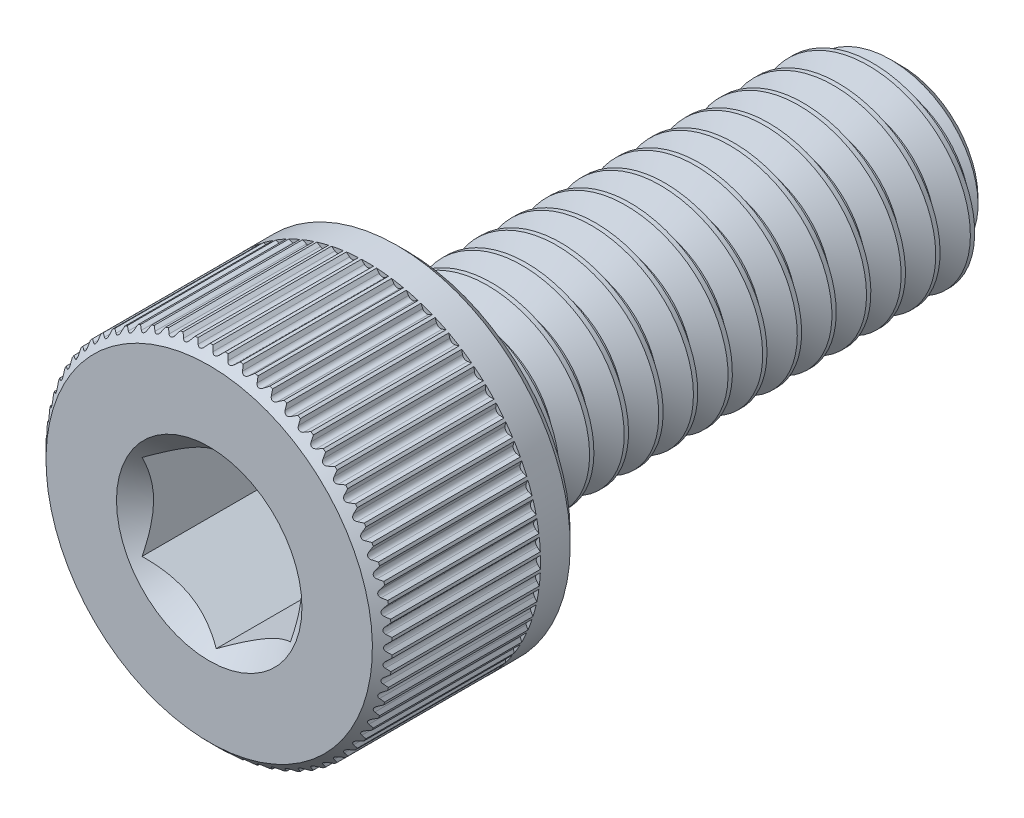
SolidWorks part; units mm, degrees
ref_plane "Front Plane" through (0, 0, 0) normal (0, 0, 1) x (1, 0, 0)
ref_plane "Top Plane" through (0, 0, 0) normal (0, 1, 0) x (1, 0, 0)
ref_plane "Right Plane" through (0, 0, 0) normal (1, 0, 0) x (0, 0, -1)
sketch "Sketch1" plane through (0, 0, 0) normal (1, 0, 0) x (0, 0, -1)
  line L0 (-7, 0) -> (7, 0) construction
  line L1 (7, 0) -> (7, 1.5453) construction
  line L2 (7, 1.5453) -> (6.5453, 2) construction
  line L3 (6.5453, 2) -> (6.475, 2) construction
  line L4 (6.475, 2) -> (-3, 2) construction
  line L5 (-3, 2) -> (-3, 3.5) construction
  line L6 (-3, 3.5) -> (-7, 3.5) construction
  line L7 (-7, 3.5) -> (-7, 0) construction
  line L8 (7, 1.5453) -> (7, 2) construction
  line L9 (6.9562, 2.0758) -> (7.3062, 1.4696) construction
  line L10 (7.3062, 1.4696) -> (7.6562, 2.0758) construction
  line L11 (7.6562, 2.0758) -> (6.9562, 2.0758) construction
  line L12 (7.3062, 2.0758) -> (7.3062, 2) construction
  line L13 (7.3062, 1.4696) -> (7.3062, 1.5453) construction
  line L14 (7.2625, 1.5453) -> (7.35, 1.5453) construction
  line L15 (7, 2) -> (7.6125, 2) construction
  line L16 (6.9781, 2.0379) -> (7.6344, 2.0379) construction
  line L17 (7, 0) -> (7, -2) construction
  line L18 (-3.2, 3.5) -> (-3, 3.3) construction
  line L19 (-6.8, 3.5) -> (-7, 3.3) construction
  line L20 (-3, 2) -> (-3, 0) construction
  line L21 (-3, 1) -> (0.3333, 1) construction
  line L22 (0.3333, 1) -> (3.6667, 1) construction
  line L23 (3.6667, 1) -> (7, 1) construction
  line L24 (0.3333, 1) -> (0.3333, 2) construction
  line L25 (0.3333, 2) -> (0.3333, 3.5) construction
  line L26 (3.6667, 1) -> (3.6667, 3.5) construction
  point P0 (-7, 1.5)
  point P3 (5.25, 2)
  point P4 (0, 0)
  point P18 (3.6667, 2)
  point P22 (7.3062, 1.5453)
  point P24 (6.475, 2)
  point P25 (7.3062, 2)
  point P28 (7.3062, 2.0379)
  point P29 (5.25, -2)
  point P30 (0.3333, 2)
  point P31 (-5, 3.5)
  point P37 (-3.7, 3.5)
  point P38 (-6.7, 3.5)
  point P45 (0.3333, 1)
  point P46 (3.6667, 1)
  dimension "D2" = 0.0875
  dimension "D7" = 0.2
  dimension "D8" = 0.2
  dimension "D9" = 0.2
  dimension "D10" = 0.1
  dimension "D11" = 0.5
  dimension "Drive Size" = 3
  dimension "Head Diameter" = 7
  dimension "Head Height" = 4
  dimension "Thread Pitch" = 0.7
  dimension "Thread Size" = 4
  dimension "Length" = 10
  dimension "D12" = 0.525
  dimension "D4" = 1.75
  dimension "D3" = 45
sketch "Sketch2" plane through (0, 0, 0) normal (1, 0, 0) x (0, 0, -1)
  line L0 (-7, 0) -> (-7, 3.3)
  line L1 (-6.8, 3.5) -> (-3.2, 3.5)
  line L2 (-3, 3.3) -> (-3, 2.2)
  line L4 (6.5453, 2) -> (7, 1.5453)
  line L5 (7, 1.5453) -> (7, 0)
  line L6 (-3, 3.5) -> (-7, 3.5) construction
  line L7 (7, 0) -> (-7, 0)
  line L8 (-6.8, 3.5) -> (-7, 3.3) construction
  line L10 (-6.8, 3.5) -> (-7, 3.3)
  line L14 (-3.2, 3.5) -> (-3, 3.3) construction
  line L16 (-3.2, 3.5) -> (-3, 3.3)
  line L17 (-3, 2) -> (-3, 3.5) construction
  line L19 (-2.8, 2) -> (6.5453, 2)
  line L20 (6.475, 2) -> (-3, 2) construction
  arc A1 (-3, 2.2) -> (-2.8, 2) centre (-2.8, 2.2) ccw
  dimension "D3" = 0.2
revolve "Revolve1" add sketch "Sketch2" angle 360 about L7
sketch "Sketch3" plane through (0, 0, 7) normal (0, 0, 1) x (1, 0, 0)
  line L1 (1.5, -0.866) -> (1.5, 0.866)
  line L2 (1.5, 0.866) -> (0, 1.7321)
  line L3 (0, 1.7321) -> (-1.5, 0.866)
  line L4 (-1.5, 0.866) -> (-1.5, -0.866)
  line L5 (-1.5, -0.866) -> (0, -1.7321)
  line L6 (0, -1.7321) -> (1.5, -0.866)
  circle A0 centre (0, 0) radius 1.5 construction
  circle A1 centre (0, 0) radius 3.5 construction
  circle A2 centre (0, 0) radius 3.5 construction
  circle A3 centre (0, 0) radius 1.7321 construction
  point P13 (0, 0)
extrude "Cut-Extrude1" cut sketch "Sketch3" against normal offset from surface (3 mm away) 1 up to face at (0, 3.3, 3)
sketch "Sketch4" plane through (0, 0, 7) normal (0, 0, 1) x (1, 0, 0)
  circle A0 centre (0, 0) radius 1.875
  dimension "D1" = 3.75
extrude "Cut-Extrude2" cut sketch "Sketch4" against normal up to vertex (2 mm away) draft 45 up to point (0, 3.5, 5)
sketch "Sketch11" plane through (0, 0, 0) normal (1, 0, 0) x (0, 0, -1)
  line L0 (-7, 0) -> (7, 0) construction
  line L1 (-7, 0) -> (7, 0) construction
  line L2 (-1.125, 0) -> (-1.125, 2) construction
  line L3 (6.475, 2) -> (-3, 2) construction
  line L4 (5.125, 0) -> (5.125, 2) construction
  line L6 (7, 1.5453) -> (7, 2) construction
  point P2 (-1.125, 0)
  point P3 (5.125, 0)
  dimension "D1" = 1.875
  dimension "D2" = 1.875
sketch "Sketch6" plane through (0, 0, -7) normal (0, 0, -1) x (-1, 0, 0)
  circle A0 centre (0, 0) radius 2
curve "Helix/Spiral1" pitch 0.7 height 10.7 turns 15.2857
sketch "Sketch10" plane through (0, 0, 0) normal (1, 0, 0) x (0, 0, -1)
  line L0 (-2.8, -3.5) -> (-2.8, 3.5)
  line L5 (-7, 0) -> (7, 0) construction
  line L6 (-2.8, 2) -> (-2.8, -2) construction
  point P3 (-2.8, 0)
split "Split1" trim tools "Sketch10" bodies to split 106 resulting bodies 114 115
sketch "Sketch7" plane through (0, 0, 0) normal (1, 0, 0) x (0, 0, -1)
  line L0 (6.9781, 2.0379) -> (7.6344, 2.0379)
  line L1 (7.6344, 2.0379) -> (7.35, 1.5453)
  line L2 (7.35, 1.5453) -> (7.2625, 1.5453)
  line L3 (7.2625, 1.5453) -> (6.9781, 2.0379)
sweep "Cut-Sweep1" cut profiles "Sketch7" path "Helix/Spiral1"
sketch "Sketch8" plane through (0, 0, 0) normal (1, 0, 0) x (0, 0, -1)
  line L0 (-3, 0) -> (-3, 2)
  line L1 (-2.8, -2) -> (-2.8, 2) construction
  line L2 (-3, 2) -> (-2.8, 2)
  line L4 (-2.8, 2) -> (-1.6453, 0)
  line L5 (-1.6453, 0) -> (-3, 0)
  line L6 (6.475, 2) -> (-3, 2) construction
  line L7 (-7, 0) -> (7, 0) construction
  dimension "D1" = 60
revolve "Revolve2" add sketch "Sketch8" angle 360 about L5
ref_plane "Plane1" through (0, 0, 7) normal (0, 0, 1) x (1, 0, 0)
sketch "Sketch12" plane through (0, 0, 7) normal (0, 0, 1) x (1, 0, 0)
  line L0 (0, 0) -> (0.1221, 3.4979) construction
  line L1 (0, 0) -> (-0.1221, 3.4979) construction
  line L2 (0, 3.4125) -> (0, 3.5875) construction
  line L3 (-0.2118, 3.5875) -> (0.2118, 3.5875)
  line L4 (-0.2118, 3.5875) -> (-0.0628, 3.4385)
  line L5 (0.0628, 3.4385) -> (0.2118, 3.5875)
  circle A0 centre (0, 0) radius 3.5 construction
  arc A1 (-0.0628, 3.4385) -> (0.0628, 3.4385) centre (0, 3.5013) ccw
  point P9 (0, 3.5875)
  point P13 (0, 3.5)
  dimension "D2" = 0.0875
extrude "Cut-Extrude3" cut sketch "Sketch12" against normal blind 3.2
pattern_circular "CirPattern1" count 72 over 360 about axis through (0, 0, 0) along (0, 0, 1) of "Cut-Extrude3"
equation "\"D2@Sketch1\" = \"Thread Pitch@Sketch1\" / 8"
equation "\"D4@Helix/Spiral1\" = \"Thread Pitch@Sketch1\""
equation "\"D7@Sketch1\" = \"Head Height@Sketch1\" * .05"
equation "\"D8@Sketch1\"=\"D7@Sketch1\""
equation "\"D9@Sketch1\"=\"D7@Sketch1\""
equation "\"D10@Sketch1\"=\"D7@Sketch1\"/2"
equation "\"D11@Sketch1\"=\"D10@Sketch1\"*5"
equation "\"D4@Sketch1\"=\"Thread Pitch@Sketch1\"*2.5"
equation "\"D12@Sketch1\"=\"Thread Pitch@Sketch1\"*.75"
equation "\"D3@Helix/Spiral1\"=\"Length@Sketch1\"+\"Thread Pitch@Sketch1\""
equation "\"D3@Sketch2\" = \"Thread Size@Sketch1\" * 0.05"
equation "\"D1@Sketch11\"=\"Length@Sketch1\"*0.1875"
equation "\"D2@Sketch11\"=\"D1@Sketch11\""
equation "\"D2@Sketch12\"=\"Head Diameter@Sketch1\"*.0125"
equation "\"D1@Cut-Extrude3\"=\"Head Height@Sketch1\"*.8"
equation "\"D1@CirPattern1\"=\"D3@CirPattern1\"/(1.25*\"D1@Sketch12\")"
equation "\"D1@Sketch4\"=\"Drive Size@Sketch1\"*1.25"
